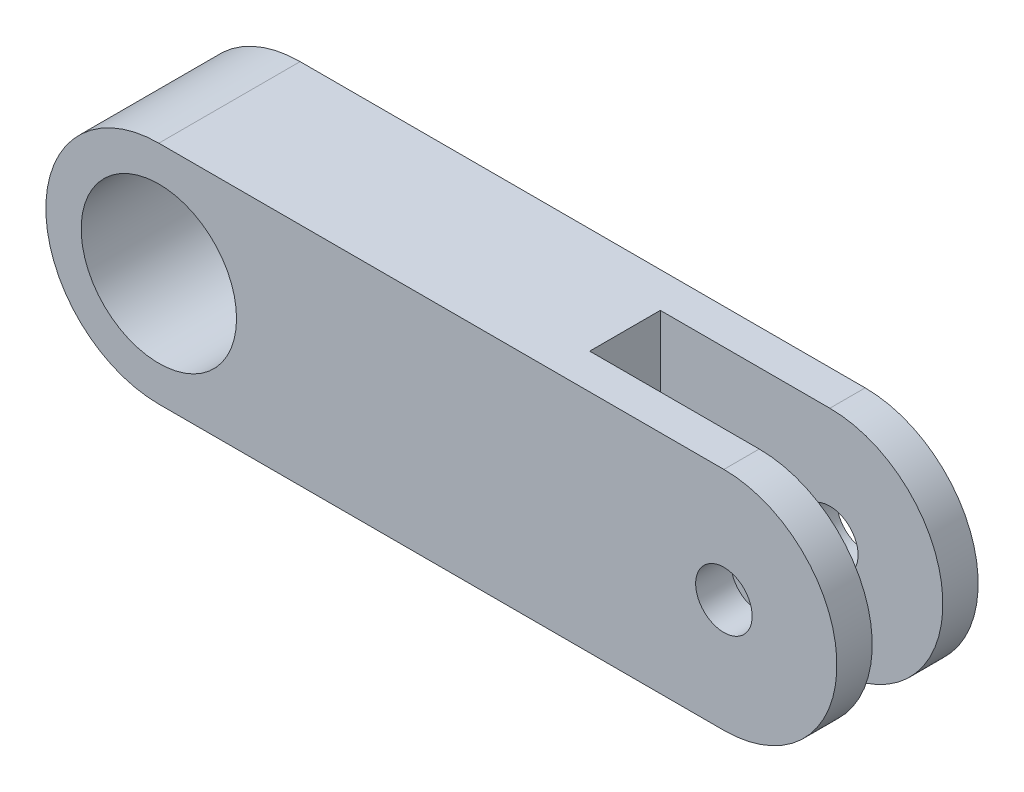
SolidWorks part; units mm, degrees
ref_plane "Front Plane" through (0, 0, 0) normal (0, 0, 1) x (1, 0, 0)
ref_plane "Top Plane" through (0, 0, 0) normal (0, 1, 0) x (1, 0, 0)
ref_plane "Right Plane" through (0, 0, 0) normal (1, 0, 0) x (0, 0, -1)
sketch "Sketch1" plane through (0, 0, 0) normal (0, 0, 1) x (1, 0, 0)
  line L0 (-10, 0) -> (10, 0) construction
  line L1 (-10, 4) -> (10, 4)
  line L2 (-10, -4) -> (10, -4)
  arc A0 (-10, 4) -> (-10, -4) centre (-10, 0) ccw
  arc A1 (10, -4) -> (10, 4) centre (10, 0) ccw
  circle A2 centre (-10, 0) radius 2.75
  circle A3 centre (10, 0) radius 1
  point P3 (0, 0)
  dimension "5.5" = 5.5
  dimension "D2" = 4
  dimension "D4" = 2
  dimension "D3" = 20
extrude "Boss-Extrude1" add sketch "Sketch1" along normal mid plane 5
sketch "Sketch5" plane through (0, 0, 0) normal (0, 0, 1) x (1, 0, 0)
  line L0 (10, 4) -> (-10, 4) construction
  line L1 (4, 4) -> (14, 4)
  line L2 (4, 4) -> (4, -4)
  line L3 (4, -4) -> (14, -4)
  line L4 (14, 4) -> (14, -4)
  line L5 (-10, -4) -> (10, -4) construction
  arc A0 (10, -4) -> (10, 4) centre (10, 0) ccw construction
  dimension "D1" = 10
extrude "Cut-Extrude1" cut sketch "Sketch5" against normal mid plane 2.5
